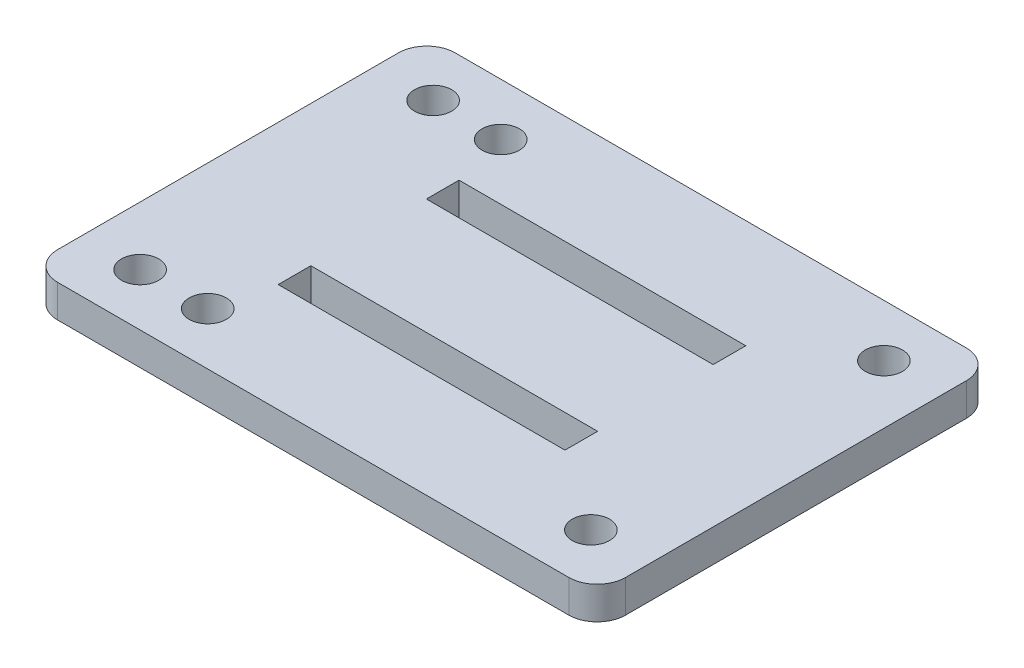
SolidWorks part; units mm, degrees
other "下垫片"
ref_plane "前视基准面" through (0, 0, 0) normal (0, 0, 1) x (1, 0, 0)
ref_plane "上视基准面" through (0, 0, 0) normal (0, 1, 0) x (1, 0, 0)
ref_plane "右视基准面" through (0, 0, 0) normal (1, 0, 0) x (0, 0, -1)
other "Configuration Table"
sketch "草图1" plane through (0, 0, 0) normal (0, 1, 0) x (1, 0, 0)
  line L0 (-89.3251, 0) -> (102.0425, 0) construction
  line L1 (0, 56.7239) -> (0, -62.578) construction
  line L2 (-20.2, -8.1375) -> (20.2, -8.1375)
  line L3 (-20.2, 12.7375) -> (20.2, 12.7375)
  line L4 (-20.2, 12.7375) -> (-20.2, 8.1375)
  line L5 (-20.2, 8.1375) -> (20.2, 8.1375)
  line L6 (20.2, 12.7375) -> (20.2, 8.1375)
  line L7 (-20.2, 12.7375) -> (20.2, 8.1375) construction
  line L8 (-20.2, 8.1375) -> (20.2, 12.7375) construction
  line L9 (20.2, -12.7375) -> (20.2, -8.1375)
  line L10 (-20.2, -12.7375) -> (20.2, -12.7375)
  line L11 (-20.2, -12.7375) -> (-20.2, -8.1375)
  circle A0 centre (-31.75, 20.6375) radius 2.625
  circle A4 centre (31.75, 20.6375) radius 2.625
  circle A5 centre (31.75, -20.6375) radius 2.625
  circle A6 centre (-31.75, -20.6375) radius 2.625
  circle A7 centre (-22.225, 20.6375) radius 2.625
  circle A8 centre (-22.225, -20.6375) radius 2.625
  point P13 (0, 10.4375)
  dimension "D5" = 5.25
  dimension "D9" = 5.25
  dimension "D7" = 10.4375
  dimension "D6" = 5.25
  dimension "D1" = 40.4
  dimension "D2" = 31.75
  dimension "D3" = 4.6
  dimension "D4" = 20.6375
  dimension "D8" = 4.6
  dimension "D10" = 40.4
  dimension "D11" = 7.9
  dimension "D12" = 31.75
  dimension "D13" = 9.525
sketch "草图3" plane through (0, 0, 0) normal (0, 1, 0) x (1, 0, 0)
  line L1 (-40, -28) -> (40, -28)
  line L2 (-40, -28) -> (-40, 28)
  line L3 (-40, 28) -> (40, 28)
  line L4 (40, -28) -> (40, 28)
  line L5 (-40, -28) -> (40, 28) construction
  line L6 (-40, 28) -> (40, -28) construction
  point P0 (0, 0)
  dimension "D1" = 56
  dimension "D2" = 80
extrude "凸台-拉伸1" add sketch "草图3" along normal blind 4.6
extrude "切除-拉伸1" cut sketch "草图1" along normal up to surface (4.6 mm away) up to face at (0, 4.6, 0)
fillet "圆角2" radius 4 4 edges at (-40, 2.3, -28) (40, 2.3, -28) (40, 2.3, 28) (-40, 2.3, 28)
